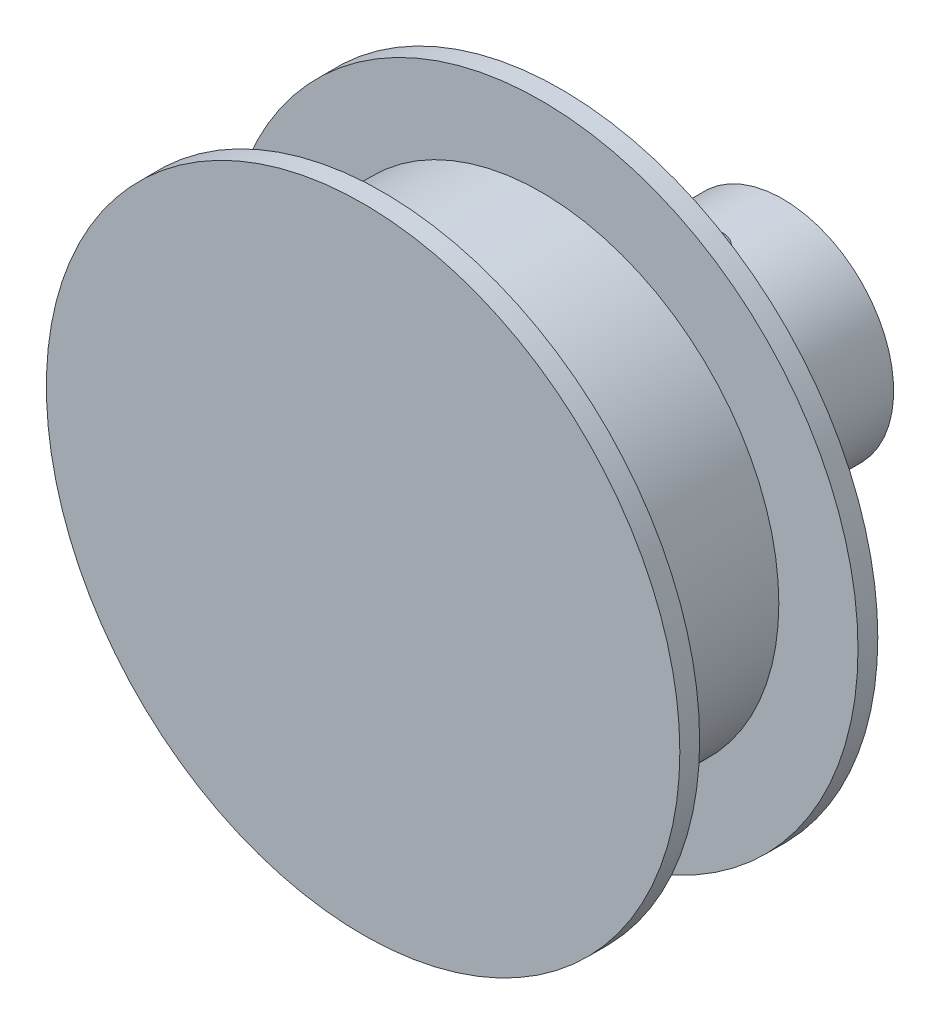
SolidWorks part; units mm, degrees
ref_plane "Front Plane" through (0, 0, 0) normal (0, 0, 1) x (1, 0, 0)
ref_plane "Top Plane" through (0, 0, 0) normal (0, 1, 0) x (1, 0, 0)
ref_plane "Right Plane" through (0, 0, 0) normal (1, 0, 0) x (0, 0, -1)
sketch "Sketch1" plane through (0, 0, 0) normal (0, 0, 1) x (1, 0, 0)
  circle A0 centre (0, 0) radius 12.7
  dimension "D1" = 25.4
extrude "Boss-Extrude1" add sketch "Sketch1" along normal blind 0.7937
sketch "Sketch2" plane through (0, 0, 0.7937) normal (0, 0, 1) x (1, 0, 0)
  circle A0 centre (0, 0) radius 9.525
  dimension "D1" = 19.05
extrude "Boss-Extrude2" add sketch "Sketch2" along normal blind 6.35
sketch "Sketch3" plane through (0, 0, 7.1437) normal (0, 0, 1) x (1, 0, 0)
  circle A0 centre (0, 0) radius 12.7
  dimension "D1" = 25.4
extrude "Boss-Extrude3" add sketch "Sketch3" along normal blind 0.7937
sketch "Sketch4" plane through (0, 0, 0) normal (0, 0, -1) x (-1, 0, 0)
  circle A0 centre (0, 0) radius 4.445
  dimension "D1" = 8.89
extrude "Boss-Extrude4" add sketch "Sketch4" along normal blind 8.89
sketch "Sketch5" plane through (0, 0, -8.89) normal (0, 0, -1) x (-1, 0, 0)
  circle A0 centre (0, 0) radius 3.175
  dimension "D1" = 6.35
extrude "Cut-Extrude1" cut sketch "Sketch5" against normal blind 9.525
sketch "Sketch6" plane through (0, 0, 0) normal (0, 1, 0) x (1, 0, 0)
  line L0 (3.175, 8.89) -> (-3.175, 8.89) construction
  circle A0 centre (0, 5.715) radius 0.7874
  dimension "D1" = 1.5748
  dimension "D2" = 3.175
extrude "Cut-Extrude2" cut sketch "Sketch6" against normal blind 25.4 and the other way blind 25.4
